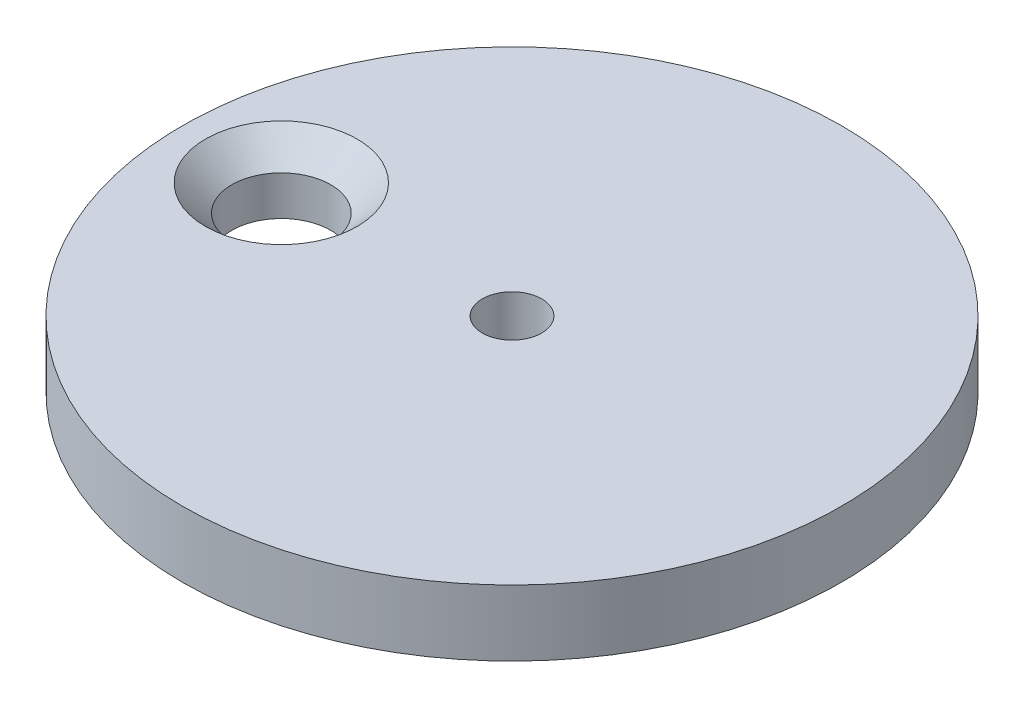
SolidWorks part; units mm, degrees
ref_plane "Front" through (0, 0, 0) normal (0, 0, 1) x (1, 0, 0)
ref_plane "Top" through (0, 0, 0) normal (0, 1, 0) x (1, 0, 0)
ref_plane "Right" through (0, 0, 0) normal (1, 0, 0) x (0, 0, -1)
sketch "Sketch1" plane through (0, 0, 0) normal (0, 1, 0) x (1, 0, 0)
  circle A0 centre (0, 0) radius 50
  circle A1 centre (-35, 0) radius 7.5
  dimension "D1" = 100
  dimension "D2" = 15
  dimension "D3" = 35
extrude "Boss-Extrude1" add sketch "Sketch1" along normal blind 10
chamfer "Chamfer1" distance 4 angle 45 1 edges at (-35, 10, 7.5)
sketch "Sketch2" plane through (0, 0, 0) normal (0, -1, 0) x (1, 0, 0)
  line L0 (-17, -2.5) -> (-4.43, -4.43)
  line L1 (0, 0) -> (-17, 0) construction
  line L2 (-17, 2.5) -> (-4.43, 4.43)
  line L3 (0, 0) -> (0, 50) construction
  line L4 (-2.5, 17) -> (-4.43, 4.43)
  line L5 (2.5, 17) -> (4.43, 4.43)
  line L6 (17, 2.5) -> (4.43, 4.43)
  line L7 (17, -2.5) -> (4.43, -4.43)
  line L8 (2.5, -17) -> (4.43, -4.43)
  line L9 (-2.5, -17) -> (-4.43, -4.43)
  arc A0 (-17, 2.5) -> (-17, -2.5) centre (-17, 0) ccw
  circle A1 centre (0, 0) radius 50 construction
  arc A2 (2.5, 17) -> (-2.5, 17) centre (0, 17) ccw
  arc A3 (17, -2.5) -> (17, 2.5) centre (17, 0) ccw
  arc A4 (-2.5, -17) -> (2.5, -17) centre (0, -17) ccw
  point P5 (-4.4046, -4.3195)
  point P6 (0, 0)
  point P7 (-4.4032, -4.3182)
  point P28 (0, 0)
  point P29 (-3.5334, -4.43)
  point P30 (0, 0)
  point P31 (-4.5545, -4.43)
  dimension "D2" = 5
  dimension "D1" = 17
  dimension "D3" = 4.43
  dimension "D4" = 4
extrude "Cut-Extrude1" cut sketch "Sketch2" against normal blind 2
sketch "Sketch3" plane through (0, 2, 0) normal (0, -1, 0) x (1, 0, 0)
  circle A0 centre (0, 0) radius 4.5
  dimension "D1" = 9
extrude "Cut-Extrude2" cut sketch "Sketch3" against normal up to next
sketch "Sketch4" plane through (0, 2, 0) normal (0, -1, 0) x (1, 0, 0)
  circle A0 centre (-16, 0) radius 1
  circle A1 centre (0, 16) radius 1
  circle A2 centre (16, 0) radius 1
  circle A3 centre (0, -16) radius 1
  point P2 (-1.0695, 15.8296)
  point P5 (0, 0)
  point P13 (0, 0)
  dimension "D2" = 2
  dimension "D1" = 16
  dimension "D3" = 4
extrude "Cut-Extrude3" cut sketch "Sketch4" against normal offset from surface (7 mm away) 1 up to face at (0, 10, 4.5)
